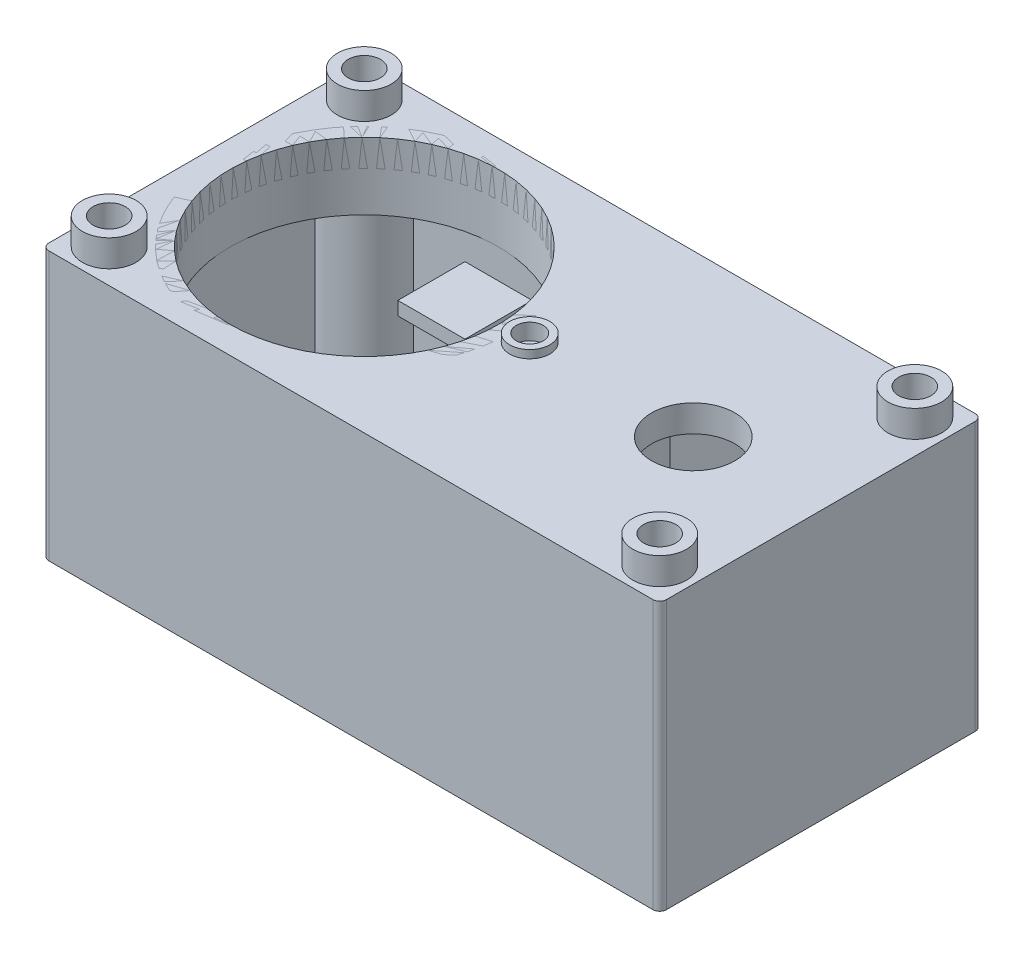
SolidWorks part; units mm, degrees
ref_plane "Ön Düzlem" through (0, 0, 0) normal (0, 0, 1) x (1, 0, 0)
ref_plane "Üst Düzlem" through (0, 0, 0) normal (0, 1, 0) x (1, 0, 0)
ref_plane "Sağ Düzlem" through (0, 0, 0) normal (1, 0, 0) x (0, 0, -1)
sketch "Sketch2" plane through (0, 0, 0) normal (0, 1, 0) x (1, 0, 0)
  line L0 (0, 6) -> (0, -6) construction
  line L1 (-11.5, -6) -> (11.5, -6)
  line L2 (-11.5, -6) -> (-11.5, 6)
  line L3 (-11.5, 6) -> (11.5, 6)
  line L4 (11.5, -6) -> (11.5, 6)
  line L5 (-11.5, -6) -> (11.5, 6) construction
  line L6 (-11.5, 6) -> (11.5, -6) construction
  circle A0 centre (-10.25, 4.75) radius 0.6
  circle A1 centre (-10.25, -4.75) radius 0.6
  circle A2 centre (10.25, -4.75) radius 0.6
  circle A3 centre (10.25, 4.75) radius 0.6
  point P0 (0, 0)
  dimension "D3" = 1.2
  dimension "D1" = 12
  dimension "D2" = 23
  dimension "D4" = 1.25
  dimension "D5" = 1.25
  dimension "D6" = 1.25
extrude "Boss-Extrude1" add sketch "Sketch2" along normal blind 10
shell "Shell1" thickness 1 removed face at (10.25, 0, 4.15)
extrude "Extrude-Thin1" add sketch "Sketch2<3>" along normal blind 1 from offset 10 thin contours A0 | A1 | A2 | A3 thin type one direction wall 0.4
sketch "Sketch2<3>" plane through (0, 0, 0) normal (0, 1, 0) x (1, 0, 0) same geometry as "Sketch2"
sketch "Sketch3" plane through (0, 10, 0) normal (0, 1, 0) x (1, 0, 0)
  line L0 (11.5, -6) -> (11.5, 6) construction
  line L1 (-11.5, -6) -> (-11.5, 6) construction
  circle A0 centre (-5.5, 0) radius 5
  circle A1 centre (6.75, 0) radius 1.55
  circle A2 centre (0.66, 0) radius 0.75
  dimension "D1" = 3.1
  dimension "D3" = 10
  dimension "D5" = 1.5
  dimension "D2" = 4.75
  dimension "D4" = 6
  dimension "D6" = 6.16
extrude "Cut-Extrude1" cut sketch "Sketch3" against normal up to next contours A0 | A1 region at (-5.5, 10, 0) region at (6.75, 10, 0)
extrude "Extrude-Thin2" add sketch "Sketch3<3>" along normal blind 0.3 thin contours A2 thin type one direction reverse wall 0.25
sketch "Sketch3<3>" plane through (0, 10, 0) normal (0, 1, 0) x (1, 0, 0) same geometry as "Sketch3"
sketch "Sketch4" plane through (0, 10, 0) normal (0, 1, 0) x (1, 0, 0)
  circle A1 centre (0.66, 0) radius 0.5
  circle A2 centre (0.66, 0) radius 0.5
  dimension "D1" = 0
extrude "Cut-Extrude2" cut sketch "Sketch4" against normal blind 0.3
sketch "Sketch5" plane through (0, 9, 0) normal (0, -1, 0) x (1, 0, 0)
  line L0 (4.1261, 5) -> (2.95, 3.8239)
  line L1 (-5.5, 5) -> (8.6697, 5) construction
  line L2 (2.95, -2.9261) -> (5.0239, -5)
  line L3 (8.6697, -5) -> (-5.5, -5) construction
  line L4 (2.95, 3.8239) -> (2.95, -2.9261)
  line L5 (10.5, 3.1697) -> (10.5, -3.1697) construction
  line L6 (8.6697, -5) -> (-8.6697, -5) construction
  point P12 (0, 0)
  point P13 (0, 0)
  dimension "D1" = 6.75
  dimension "D2" = 135
  dimension "D3" = 7.55
extrude "Extrude-Thin3" add sketch "Sketch5" along normal blind 5 thin thin type one direction wall 0.5
extrude "Extrude-Thin4" add sketch "Sketch3<6>" against normal blind 2.5 separate body thin contours A0 thin type one direction wall 0.5
sketch "Sketch3<6>" plane through (0, 10, 0) normal (0, 1, 0) x (1, 0, 0) same geometry as "Sketch3"
sketch "Sketch8" plane through (0, 10, 0) normal (0, 1, 0) x (1, 0, 0)
  line L0 (-5.5, 5) -> (-8.6697, 5) construction
  line L1 (-6.75, 5) -> (-4.25, 5)
  line L2 (-6.75, 5) -> (-6.75, 2.5)
  line L3 (-6.75, 2.5) -> (-4.25, 2.5)
  line L4 (-4.25, 5) -> (-4.25, 2.5)
  line L5 (-5.5, 0) -> (-7.1152, 0) construction
  line L6 (-4.25, -5) -> (-4.25, -2.5)
  line L7 (-6.75, -2.5) -> (-4.25, -2.5)
  line L8 (-6.75, -5) -> (-6.75, -2.5)
  line L9 (-6.75, -5) -> (-4.25, -5)
  point P6 (-5.5, 2.5)
  dimension "D1" = 2.5
extrude "Boss-Extrude3" add sketch "Sketch8" against normal blind 0.5 from offset 3.6 offset against normal yes
fillet "Fillet1" radius 0.25 4 edges at (-11.5, 5, 6) (-11.5, 5, -6) (11.5, 5, 6) (11.5, 5, -6)
